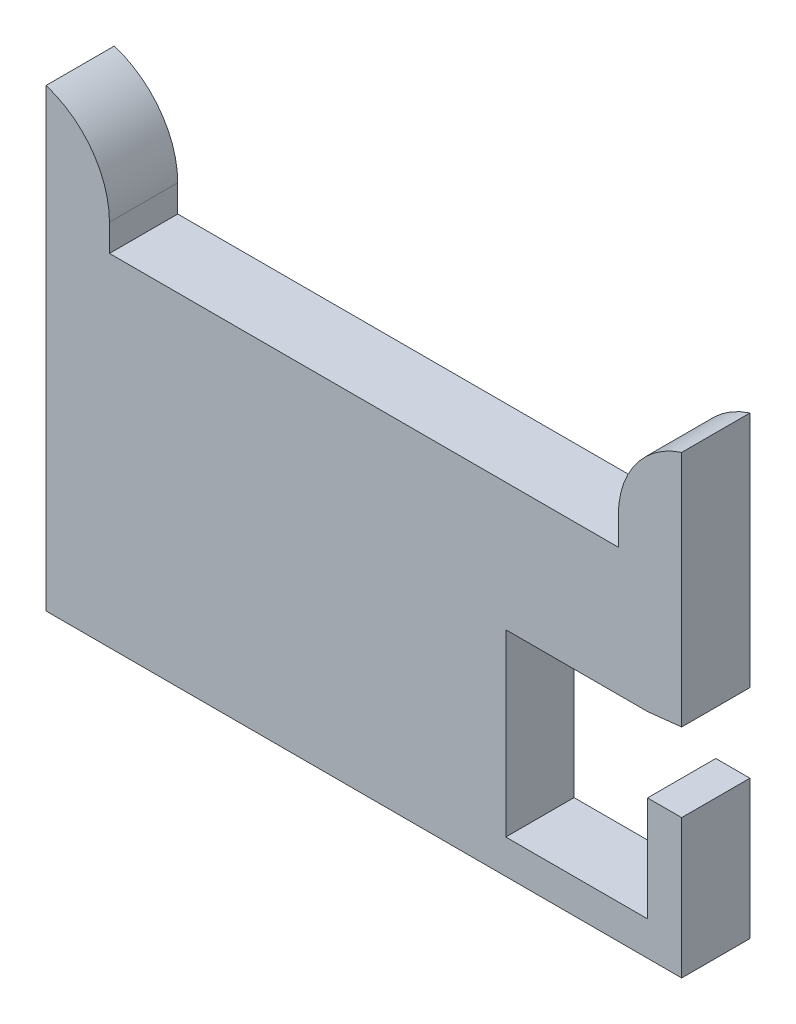
SolidWorks part; units mm, degrees
ref_plane "Front Plane" through (0, 0, 0) normal (0, 0, 1) x (1, 0, 0)
ref_plane "Top Plane" through (0, 0, 0) normal (0, 1, 0) x (1, 0, 0)
ref_plane "Right Plane" through (0, 0, 0) normal (1, 0, 0) x (0, 0, -1)
sketch "Sketch1" plane through (0, 0, 0) normal (0, 0, 1) x (1, 0, 0)
  line L0 (0, 36.6169) -> (0, -36.6169) construction
  line L1 (-27.9279, -36.6169) -> (27.9279, -36.6169)
  line L2 (27.9279, -36.6169) -> (27.9279, 3.3831)
  line L3 (27.9279, 3.3831) -> (22.3557, 3.3831)
  line L4 (22.3557, 3.3831) -> (22.3557, -6.6169)
  line L5 (22.3557, -6.6169) -> (-22.3557, -6.6169)
  line L6 (-27.9279, -36.6169) -> (-27.9279, 3.3831)
  line L7 (-22.3557, 3.3831) -> (-22.3557, -6.6169)
  line L8 (-27.9279, 3.3831) -> (-22.3557, 3.3831)
  point P12 (0, -6.6169)
  dimension "D1" = 40
  dimension "D2" = 30
extrude "Boss-Extrude1" add sketch "Sketch1" along normal blind 6
fillet "Fillet7" radius 8 1 edges at (-22.3557, 3.3831, 3)
fillet "Fillet8" radius 8 1 edges at (22.3557, 3.3831, 3)
sketch "Sketch3" plane through (0, 0, 6) normal (0, 0, 1) x (1, 0, 0)
  line L0 (27.9279, -36.6169) -> (27.9279, 3.3831) construction
  line L1 (12.471, -17.8382) -> (24.9279, -17.8382)
  line L2 (12.471, -17.8382) -> (12.471, -33.6169)
  line L3 (12.471, -33.6169) -> (24.9279, -33.6169)
  line L4 (24.9279, -17.8382) -> (24.9279, -33.6169)
  line L5 (12.471, -17.8382) -> (24.9279, -33.6169) construction
  line L6 (12.471, -33.6169) -> (24.9279, -17.8382) construction
  line L7 (-27.9279, -36.6169) -> (27.9279, -36.6169) construction
  dimension "D1" = 3
  dimension "D2" = 3
extrude "Cut-Extrude1" cut sketch "Sketch3" against normal through all
sketch "Sketch4" plane through (0, 0, 6) normal (0, 0, 1) x (1, 0, 0)
  line L0 (24.9279, -24.4102) -> (27.9279, -24.4102)
  line L1 (24.9279, -33.6169) -> (24.9279, -17.8382) construction
  line L2 (27.9279, -36.6169) -> (27.9279, 3.3831) construction
  line L3 (27.9279, -17.5169) -> (24.9279, -17.8382)
  line L4 (24.9279, -17.8382) -> (24.9279, -24.4102)
extrude "Cut-Extrude2" cut sketch "Sketch4" against normal through all and the other way through all
